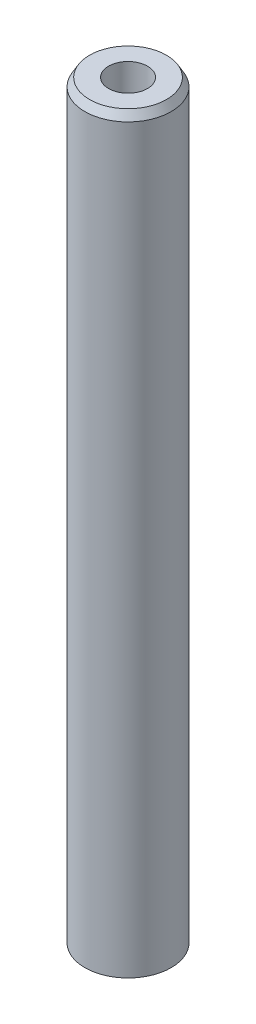
SolidWorks part; units mm, degrees
ref_plane "Front Plane" through (0, 0, 0) normal (0, 0, 1) x (1, 0, 0)
ref_plane "Top Plane" through (0, 0, 0) normal (0, 1, 0) x (1, 0, 0)
ref_plane "Right Plane" through (0, 0, 0) normal (1, 0, 0) x (0, 0, -1)
sketch "Sketch1" plane through (0, 0, 0) normal (0, 1, 0) x (1, 0, 0)
  circle A0 centre (0, 0) radius 27.5
  dimension "SHAFT_OD" = 55
extrude "Boss-Extrude1" add sketch "Sketch1" along normal blind 480.8525
sketch "Sketch2" plane through (0, 0, 0) normal (0, 1, 0) x (1, 0, 0)
  circle A0 centre (0, 0) radius 12.4075
  dimension "BORE_D" = 24.815
extrude "Cut-Extrude1" cut sketch "Sketch2" along normal through all
chamfer "Chamfer1" distance 5.1778 angle 30 2 edges at (0, 480.8525, 27.5) (0, 0, 27.5) first distance on face at (0, 480.8525, 27.5) first distance on face at (0, 0, 12.4075)
